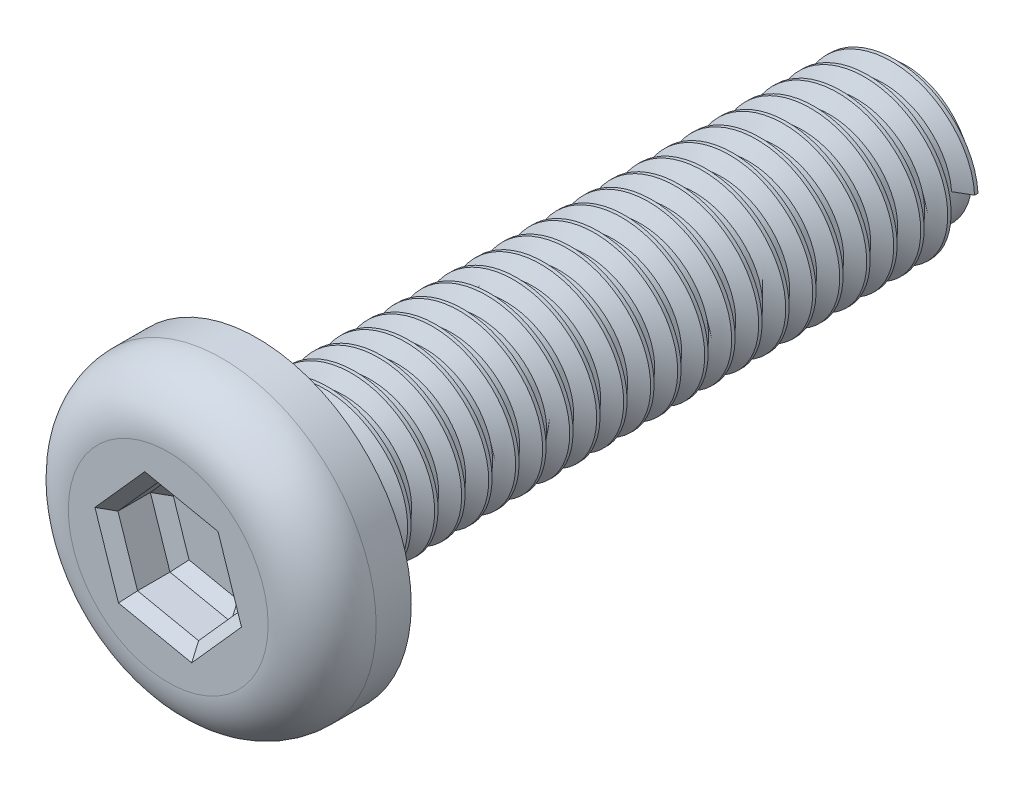
SolidWorks part; units mm, degrees
ref_plane "前视基准面" through (0, 0, 0) normal (0, 0, 1) x (1, 0, 0)
ref_plane "上视基准面" through (0, 0, 0) normal (0, 1, 0) x (1, 0, 0)
ref_plane "右视基准面" through (0, 0, 0) normal (1, 0, 0) x (0, 0, -1)
sketch "草图1" plane through (0, 0, 0) normal (0, 0, 1) x (1, 0, 0)
  circle A0 centre (0, 0) radius 2.85
  dimension "D1" = 5.7
extrude "凸台-拉伸1" add sketch "草图1" along normal blind 1.65
sketch "草图2" plane through (0, 0, 0) normal (0, 0, -1) x (-1, 0, 0)
  circle A0 centre (0, 0) radius 1.2295
  dimension "D1" = 2.459
extrude "凸台-拉伸2" add sketch "草图2" along normal blind 12
fillet "圆角1" radius 1 1 edges at (2.85, 0, 1.65)
sketch "草图3" plane through (0, 0, 1.65) normal (0, 0, 1) x (1, 0, 0)
  line L1 (0.3622, -1.0964) -> (1.1306, -0.2345)
  line L2 (1.1306, -0.2345) -> (0.7684, 0.8619)
  line L3 (0.7684, 0.8619) -> (-0.3622, 1.0964)
  line L4 (-0.3622, 1.0964) -> (-1.1306, 0.2345)
  line L5 (-1.1306, 0.2345) -> (-0.7684, -0.8619)
  line L6 (-0.7684, -0.8619) -> (0.3622, -1.0964)
  circle A0 centre (0, 0) radius 1 construction
  dimension "D1" = 2
extrude "切除-拉伸1" cut sketch "草图3" against normal blind 1
chamfer "倒角1" distance 0.2 angle 45 12 edges at (0.7464, -0.6655, 1.65) (0.9495, 0.3137, 1.65) (0.2031, 0.9792, 1.65) (-0.7464, 0.6655, 1.65) (-0.9495, -0.3137, 1.65) (-0.2031, -0.9792, 1.65) (-0.9495, -0.3137, 0.65) (-0.7464, 0.6655, 0.65) (0.2031, 0.9792, 0.65) (0.9495, 0.3137, 0.65) (0.7464, -0.6655, 0.65) (-0.2031, -0.9792, 0.65)
thread "螺纹线1" pitch 0.5 method extrude profile "螺纹线轮廓2" start angle 0, offset 0, length 0, pitch 0.5, diameter 2.459
ref_plane "基准面2" through (1.2295, 0, -12) normal (0, -1, 0) x (1, 0, 0)
sketch "螺纹线轮廓2" plane through (1.2295, 0, -12) normal (0, -1, 0) x (1, 0, 0)
  line L0 (0, 0) -> (0, 0.5) construction
  line L1 (0, 0) -> (0.2706, 0.1562)
  line L2 (0.2706, 0.1562) -> (0.2706, 0.2187)
  line L3 (0.2706, 0.2187) -> (0, 0.375)
  line L4 (0.2706, 0.1875) -> (0, 0.1875) construction
  line L11 (0, 0) -> (0, 0.375)
  point P2 (0, 0)
  dimension "Pitch" = 0.5
  dimension "Profile_Angle" = 60
  dimension "Profile_Land" = 0.0625
  dimension "Profile_Height" = 0.2706
